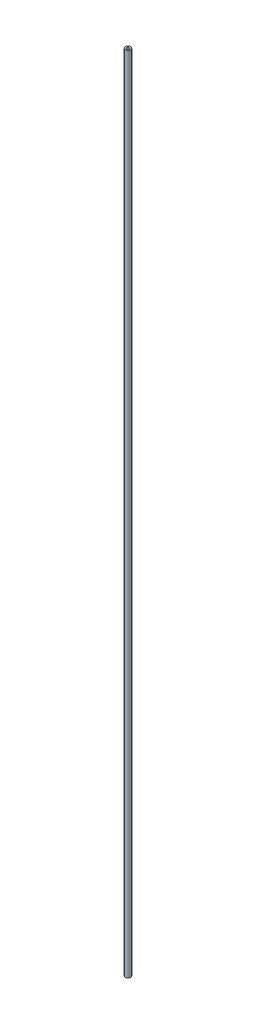
SolidWorks part; units mm, degrees
ref_plane "Front Plane" through (0, 0, 0) normal (0, 0, 1) x (1, 0, 0)
ref_plane "Top Plane" through (0, 0, 0) normal (0, 1, 0) x (1, 0, 0)
ref_plane "Right Plane" through (0, 0, 0) normal (1, 0, 0) x (0, 0, -1)
sketch "Sketch1" plane through (0, 0, 0) normal (0, 1, 0) x (1, 0, 0)
  circle A0 centre (0, 0) radius 0.5
  circle A1 centre (0, 0) radius 1
  dimension "D1" = 2
  dimension "D2" = 1
extrude "Boss-Extrude1" add sketch "Sketch1" along normal blind 150 and the other way blind 150
